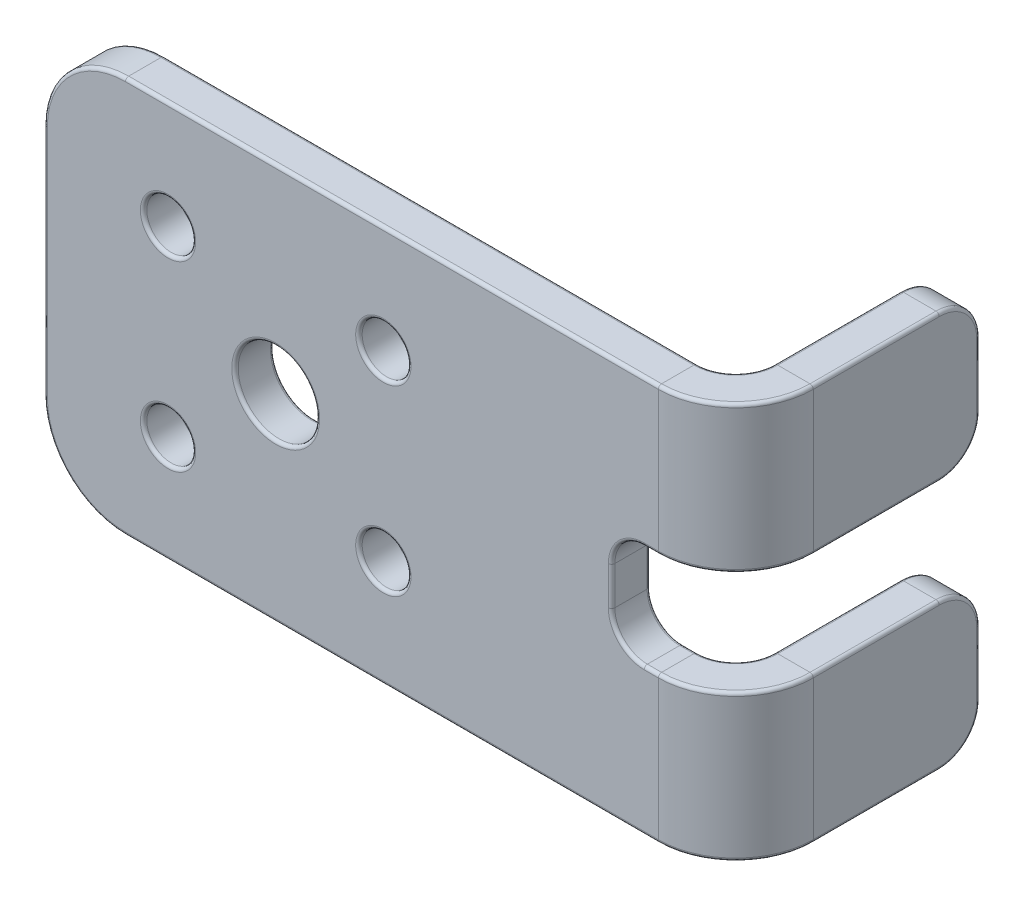
SolidWorks part; units mm, degrees
note: The reader was unsure of these and kept them because the rebuilt part matched: flange length of "Edge-Flange1".
material "moto_teal"
ref_plane "Front Plane" through (0, 0, 0) normal (0, 0, 1) x (1, 0, 0)
ref_plane "Top Plane" through (0, 0, 0) normal (0, 1, 0) x (1, 0, 0)
ref_plane "Right Plane" through (0, 0, 0) normal (1, 0, 0) x (0, 0, -1)
sketch "Sketch1" plane through (0, 0, 0) normal (0, 0, 1) x (1, 0, 0)
  line L0 (27.2404, 6.355) -> (42.5, 6.355)
  line L1 (-42.5, -24.355) -> (42.5, -24.355)
  line L2 (-42.5, -24.355) -> (-42.5, 24.355)
  line L3 (-42.5, 24.355) -> (42.5, 24.355)
  line L5 (-42.5, -24.355) -> (42.5, 24.355) construction
  line L6 (-42.5, 24.355) -> (42.5, -24.355) construction
  line L11 (27.2404, 6.355) -> (27.2404, -6.355)
  line L13 (42.5, -6.355) -> (27.2404, -6.355)
  line L14 (42.5, 24.355) -> (42.5, 6.355)
  line L15 (42.5, -6.355) -> (42.5, -24.355)
  point P0 (0, 0)
  point P6 (35, 0)
  dimension "D1" = 85
  dimension "D2" = 48.71
  dimension "D3" = 18
  dimension "D4" = 18
base flange "Base-Flange2" sketch "Sketch1" thickness 4.76 reverse thickness direction no parameters "D1"=0.7366
fillet "Fillet1" radius 4 2 edges at (27.2404, -6.355, -2.38) (27.2404, 6.355, -2.38)
fillet "Fillet2" radius 10 2 edges at (-42.5, -24.355, -2.38) (-42.5, 24.355, -2.38)
sketch "Sketch16" plane through (0, 0, 0) normal (0, 0, 1) x (1, 0, 0)
  line L0 (-27.27, 11.205) -> (-14.04, 11.205)
  line L1 (-14.04, 11.205) -> (-14.04, 15.968)
  line L2 (-27.27, 0) -> (-22.4249, 0)
  line L3 (-27.27, 11.205) -> (-27.27, 0)
  line L12 (42.5, 6.355) -> (42.5, 24.355)
  line L13 (42.5, 6.355) -> (42.5, 24.355)
  line L14 (42.5, -24.355) -> (42.5, -6.355)
  line L15 (42.5, -24.355) -> (42.5, -6.355)
  line L16 (-42.5, 14.355) -> (-42.5, -14.355)
  line L17 (-32.5, -24.355) -> (42.5, -24.355)
  line L19 (42.5, -6.355) -> (31.2404, -6.355)
  line L20 (27.2404, -2.355) -> (27.2404, 2.355)
  line L21 (31.2404, 6.355) -> (42.5, 6.355)
  line L23 (42.5, 24.355) -> (-32.5, 24.355)
  line L24 (-42.5, 14.355) -> (-42.5, -14.355)
  line L25 (-32.5, -24.355) -> (42.5, -24.355)
  line L27 (42.5, -6.355) -> (31.2404, -6.355)
  line L28 (27.2404, -2.355) -> (27.2404, 2.355)
  line L29 (31.2404, 6.355) -> (42.5, 6.355)
  line L31 (42.5, 24.355) -> (-32.5, 24.355)
  circle A4 centre (-27.27, 11.205) radius 3
  circle A6 centre (-0.81, 11.205) radius 3
  circle A7 centre (-0.81, -11.205) radius 3
  circle A8 centre (-14.04, 0) radius 5
  circle A16 centre (-27.27, -11.205) radius 3
  arc A17 (-42.5, -14.355) -> (-32.5, -24.355) centre (-32.5, -14.355) ccw
  arc A18 (-42.5, -14.355) -> (-32.5, -24.355) centre (-32.5, -14.355) ccw
  arc A19 (27.2404, -2.355) -> (31.2404, -6.355) centre (31.2404, -2.355) ccw
  arc A20 (27.2404, -2.355) -> (31.2404, -6.355) centre (31.2404, -2.355) ccw
  arc A21 (31.2404, 6.355) -> (27.2404, 2.355) centre (31.2404, 2.355) ccw
  arc A22 (31.2404, 6.355) -> (27.2404, 2.355) centre (31.2404, 2.355) ccw
  arc A23 (-32.5, 24.355) -> (-42.5, 14.355) centre (-32.5, 14.355) ccw
  arc A24 (-32.5, 24.355) -> (-42.5, 14.355) centre (-32.5, 14.355) ccw
  dimension "D2" = 13.23
  dimension "D5" = 10
  dimension "D3" = 13.15
  dimension "D4" = 15.23
  dimension "D7" = 11.205
  dimension "D1" = 0
edge flange "Edge-Flange1" sketch "Sketch21" flange profiles "Sketch21", "Sketch22" flange angle 90 flange length 30 flange position material inside bend radius 4.76 thickness 4.76 relief rectangular parameters "D6"=10, "D8"=1
sketch "Sketch21" plane through (42.5, 0, -4.76) normal (1, 0, 0) x (0, -1, 0)
  line L0 (-6.355, 0) -> (-24.355, 0) construction
  line L1 (-6.355, 0) -> (-24.355, 0)
  line L2 (-24.355, 0) -> (-24.355, 25.24)
  line L3 (-24.355, 25.24) -> (-6.355, 25.24)
  line L4 (-6.355, 25.24) -> (-6.355, 0)
sketch "Sketch22" plane through (42.5, 0, -4.76) normal (1, 0, 0) x (0, -1, 0)
  line L0 (24.355, 0) -> (6.355, 0) construction
  line L1 (24.355, 0) -> (6.355, 0)
  line L2 (6.355, 0) -> (6.355, 25.24)
  line L3 (6.355, 25.24) -> (24.355, 25.24)
  line L4 (24.355, 25.24) -> (24.355, 0)
bend "EdgeBend1" bend radius 4.76 bend angle 90 parameters "D5"=1
bend "EdgeBend2" bend radius 4.76 bend angle 90 parameters "D5"=2
fillet "Fillet3" radius 5 4 edges at (40.12, -24.355, -30) (40.12, -6.355, -30) (40.12, 6.355, -30) (40.12, 24.355, -30)
extrude "Cut-Extrude2" cut sketch "Sketch16" against normal blind 10 contours L0 A4 L3 | L3 A4 L0 | A6 | A7 | A16 | A8 normal cut yes
fillet "Fillet4" radius 0.4 10 edges at (2.19, -11.205, 0) (-24.27, -11.205, 0) (-24.27, 11.205, 0) (2.19, 11.205, 0) (-9.04, 0, 0) (2.19, 11.205, -4.76) (2.19, -11.205, -4.76) (-9.04, 0, -4.76) (-24.27, 11.205, -4.76) (-24.27, -11.205, -4.76)
fillet "Fillet5" radius 0.4 48 edges at (39.7117, -6.355, -2.7883) (39.7117, -24.355, -2.7883) (36.3458, -6.355, -6.1542) (36.3458, -24.355, -6.1542) (37.74, -24.355, -17.26) (42.5, -24.355, -17.26) (37.74, -15.355, -30) (42.5, -15.355, -30) (37.74, -6.355, -17.26) (37.74, -7.8195, -28.5355) (37.74, -22.8905, -28.5355) (42.5, -6.355, -17.26) (42.5, -7.8195, -28.5355) (42.5, -22.8905, -28.5355) (37.74, 15.355, -30) (42.5, 15.355, -30) (37.74, 24.355, -17.26) (37.74, 22.8905, -28.5355) (37.74, 7.8195, -28.5355) (42.5, 24.355, -17.26) (42.5, 22.8905, -28.5355) (42.5, 7.8195, -28.5355) (27.2404, 0, 0) (27.2404, 0, -4.76) (32.1102, 6.355, 0) (32.1102, 6.355, -4.76) (28.412, -5.1834, 0) (28.412, -5.1834, -4.76) (28.412, 5.1834, 0) (28.412, 5.1834, -4.76) (-42.5, 0, 0) (-42.5, 0, -4.76) (0.24, -24.355, 0) (-39.5711, 21.4261, 0) (-39.5711, -21.4261, 0) (0.24, -24.355, -4.76) (-39.5711, 21.4261, -4.76) (-39.5711, -21.4261, -4.76) (0.24, 24.355, 0) (0.24, 24.355, -4.76) (32.1102, -6.355, -4.76) (32.1102, -6.355, 0) (39.7117, 24.355, -2.7883) (39.7117, 6.355, -2.7883) (36.3458, 24.355, -6.1542) (36.3458, 6.355, -6.1542) (37.74, 6.355, -17.26) (42.5, 6.355, -17.26)
sketch "Bend-Lines3" [suppressed] plane through (0, 0, 0) normal (0, 1, 0) x (1, 0, 0)
sketch "Bounding-Box3" [suppressed] plane through (0, 0, 0) normal (0, 1, 0) x (1, 0, 0)
sheet metal parameters "Sheet-Metal2" thickness 4.76 parameters "D1"=0.7366
flat pattern "Flat-Pattern2" [suppressed]
sketch "Bend-Lines4" plane through (0, 0, 0) normal (0, 1, 0) x (1, 0, 0)
sketch3d "Bounding-Box4" [suppressed]
  line L0 (-42.5, -24.355, 0) -> (42.5, -24.355, 0) construction
  line L1 (-42.5, 24.355, 0) -> (42.5, 24.355, 0) construction
  line L2 (-42.5, -24.355, 0) -> (-42.5, 24.355, 0) construction
  line L3 (42.5, -24.355, 0) -> (42.5, 24.355, 0) construction
sheet metal parameters "Sheet-Metal5" thickness 4.76 parameters "D1"=0.7366
flat pattern "Flat-Pattern2"
sketch "Bend-Lines4" plane through (0, 0, 0) normal (0, 0, 1) x (1, 0, 0)
  line L0 (38.5877, -24.355) -> (38.5877, -6.355) construction
  line L1 (38.5877, 6.355) -> (38.5877, 24.355) construction
  line L2 (38.5877, -24.355) -> (38.5877, -6.355) construction
  line L3 (38.5877, 6.355) -> (38.5877, 24.355) construction
sketch3d "Bounding-Box4" [suppressed]
  line L0 (-42.5, -24.355, 0) -> (64.6755, -24.355, 0) construction
  line L1 (-42.5, 24.355, 0) -> (64.6755, 24.355, 0) construction
  line L2 (-42.5, -24.355, 0) -> (-42.5, 24.355, 0) construction
  line L3 (64.6755, -24.355, 0) -> (64.6755, 24.355, 0) construction
bend of the flat pattern "Flatten-<EdgeBend1>1"
bend of the flat pattern "Flatten-<EdgeBend2>1"
sheet metal parameters "Sheet-Metal6" thickness 4.76 parameters "D1"=0.7366
flat pattern "Flat-Pattern2"
sketch "Bend-Lines4" plane through (0, 0, 0) normal (0, 0, 1) x (1, 0, 0)
  line L0 (38.5877, -23.955) -> (38.5877, -6.755) construction
  line L1 (38.5877, 6.755) -> (38.5877, 23.955) construction
  line L2 (38.5877, -23.955) -> (38.5877, -6.755) construction
  line L3 (38.5877, 6.755) -> (38.5877, 23.955) construction
sketch3d "Bounding-Box4" [suppressed]
  line L0 (-42.5, -24.355, 0) -> (64.6755, -24.355, 0) construction
  line L1 (-42.5, 24.355, 0) -> (64.6755, 24.355, 0) construction
  line L2 (-42.5, -24.355, 0) -> (-42.5, 24.355, 0) construction
  line L3 (64.6755, -24.355, 0) -> (64.6755, 24.355, 0) construction
bend of the flat pattern "Flatten-<EdgeBend1>1"
bend of the flat pattern "Flatten-<EdgeBend2>1"
